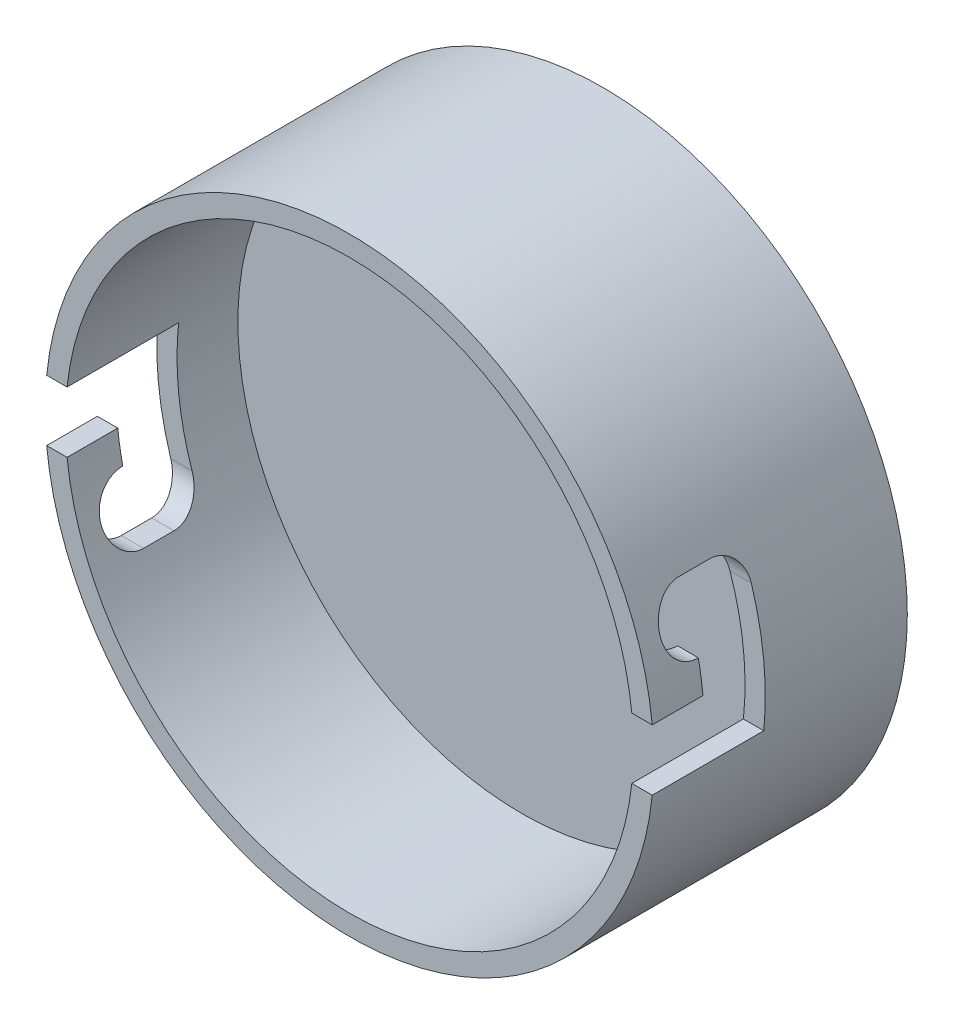
SolidWorks part; units mm, degrees
ref_plane "Front Plane" through (0, 0, 0) normal (0, 0, 1) x (1, 0, 0)
ref_plane "Top Plane" through (0, 0, 0) normal (0, 1, 0) x (1, 0, 0)
ref_plane "Right Plane" through (0, 0, 0) normal (1, 0, 0) x (0, 0, -1)
sketch "Sketch1" plane through (0, 0, 0) normal (0, 0, 1) x (1, 0, 0)
  circle A0 centre (0, 0) radius 30
  dimension "D1" = 60
extrude "Boss-Extrude1" add sketch "Sketch1" along normal blind 8
sketch "Sketch2" plane through (0, 0, 8) normal (0, 0, 1) x (1, 0, 0)
  circle A0 centre (0, 0) radius 30
  circle A1 centre (0, 0) radius 28
  dimension "D1" = 60
  dimension "D2" = 2
extrude "Boss-Extrude2" add sketch "Sketch2" along normal blind 17
sketch "Sketch3" plane through (0, 0, 0) normal (1, 0, 0) x (0, 0, -1)
  line L0 (-25, 0) -> (0, 0) construction
  line L1 (-25, 30) -> (-25, -30) construction
  line L2 (-25, 3) -> (-20, 3)
  line L3 (-25, -3) -> (-20, -3)
  line L4 (-20, -3) -> (-20, -6)
  line L5 (-14, -9) -> (-14, 3)
  line L6 (-14, 3) -> (-20, 3)
  line L7 (-25, -3) -> (-25, 3)
  line L8 (-17, -12) -> (-20, -12)
  arc A1 (-20, -6) -> (-20, -12) centre (-20, -9) ccw
  arc A2 (-17, -12) -> (-14, -9) centre (-17, -9) ccw
  dimension "D4" = 12
  dimension "D3" = 3
  dimension "D5" = 6
  dimension "D9" = 6
  dimension "D1" = 3
  dimension "D2" = 5
  dimension "D6" = 3
  dimension "D7" = 3
extrude "Cut-Extrude1" cut sketch "Sketch3" against normal blind 39
pattern_circular "CirPattern1" count 2 over 180 about axis through (0, 0, 8) along (0, 0, 1) of "Cut-Extrude1"
sketch "Sketch4" plane through (0, 0, 0) normal (0, 0, -1) x (-1, 0, 0)
  line L0 (-3.375, 24) -> (-3.375, 12.0244)
  line L1 (3.375, 24) -> (3.375, 12.0244)
  arc A0 (-5.912, 4.4921) -> (5.912, 4.4921) centre (0, 0) ccw
  arc A1 (3.375, 24) -> (-3.375, 24) centre (0, 24) ccw
  arc A2 (5.912, 4.4921) -> (3.375, 12.0244) centre (15.825, 12.0244) cw
  arc A3 (-5.912, 4.4921) -> (-3.375, 12.0244) centre (-15.825, 12.0244) ccw
  circle A4 centre (0, 24) radius 1.5
  circle A5 centre (0, 20) radius 1.5
  point P14 (0, 27.375)
  point P15 (0, -7.425)
  dimension "D1" = 12.45
  dimension "D2" = 4
  dimension "D3" = 3
  dimension "D4" = 3.375
  dimension "D5" = 34.8
  dimension "D6" = 7.425
extrude "Cut-Extrude2" cut sketch "Sketch4" against normal blind 4 contours A3 L0 A1 L1 A2 A0
extrude "Cut-Extrude3" cut sketch "Sketch4<4>" against normal blind 20 contours A4 | A5 region at (0, 24, 0)
sketch "Sketch4<4>" plane through (0, 0, 0) normal (0, 0, -1) x (-1, 0, 0) same geometry as "Sketch4"
equation "\"90eg\"=21"
equation "\"180eg\"=360"
